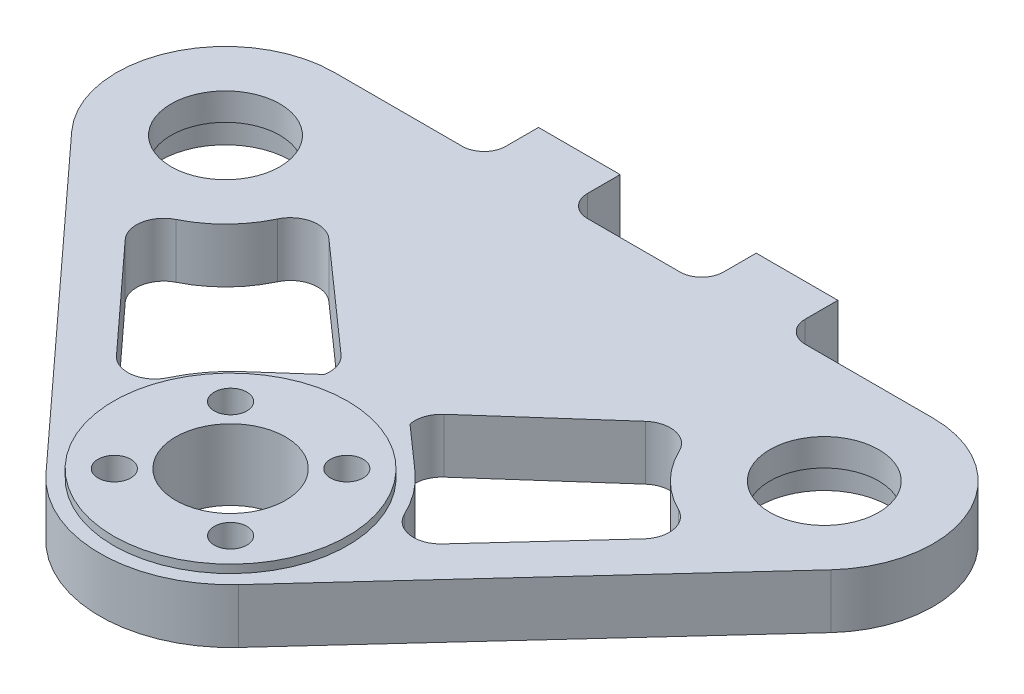
SolidWorks part; units mm, degrees
material "PLA Infill"
ref_plane "Front Plane" through (0, 0, 0) normal (0, 0, 1) x (1, 0, 0)
ref_plane "Top Plane" through (0, 0, 0) normal (0, 1, 0) x (1, 0, 0)
ref_plane "Right Plane" through (0, 0, 0) normal (1, 0, 0) x (0, 0, -1)
sketch "Sketch1" plane through (0, 0, 0) normal (0, 1, 0) x (1, 0, 0)
  line L0 (0, 0) -> (55, 54.0672) construction
  line L1 (55, 54.0672) -> (-55, 54.0672) construction
  line L2 (-55, 54.0672) -> (0, 0) construction
  line L3 (-69.7415, 40.551) -> (-17.6898, -16.2194)
  line L4 (-41.7379, 69.0378) -> (15.9145, 17.9646)
  line L5 (-47.6255, 28.2677) -> (-29.9271, 8.9649)
  line L6 (-29.0781, 47.135) -> (-9.4754, 29.7694)
  circle A0 centre (0, 0) radius 10.1
  circle A1 centre (-55, 54.0672) radius 10
  circle A2 centre (0, 0) radius 24 construction
  circle A3 centre (-55, 54.0672) radius 20 construction
  arc A4 (-69.7415, 40.551) -> (-41.7379, 69.0378) centre (-55, 54.0672) cw
  arc A5 (-17.6898, -16.2194) -> (15.9145, 17.9646) centre (0, 0) ccw
  arc A6 (-46.1521, 36.1308) -> (-36.9149, 45.5274) centre (-55, 54.0672) ccw
  arc A7 (-21.7173, 10.2157) -> (-10.5856, 21.5394) centre (0, 0) cw
  arc A8 (-29.9271, 8.9649) -> (-21.7173, 10.2157) centre (-26.2417, 12.3439) ccw
  arc A9 (-9.4754, 29.7694) -> (-10.5856, 21.5394) centre (-12.7909, 26.0268) cw
  arc A10 (-29.0781, 47.135) -> (-36.9149, 45.5274) centre (-32.3936, 43.3924) ccw
  arc A11 (-47.6255, 28.2677) -> (-46.1521, 36.1308) centre (-43.9401, 31.6467) cw
  point P22 (-23.8825, 2.3723)
  point P25 (-2.7804, 23.8384)
  point P28 (-35.0663, 52.4399)
  point P31 (-53.032, 34.1643)
  dimension "D3" = 20.2
  dimension "D4" = 20
  dimension "D5" = 48
  dimension "D6" = 40
  dimension "D9" = 5
  dimension "D1" = 77.125
  dimension "D2" = 110
  dimension "D7" = 8
  dimension "D8" = 8
extrude "Main Body" add sketch "Sketch1" along normal blind 10
sketch "Sketch2" plane through (0, 0, 0) normal (0, -1, 0) x (1, 0, 0)
  circle A0 centre (-55, -54.0672) radius 10 construction
  circle A1 centre (-55, -54.0672) radius 10 construction
  circle A2 centre (-55, -54.0672) radius 12
  dimension "D1" = 24
extrude "Bearing Recess" cut sketch "Sketch2" against normal blind 5
sketch "Sketch3" plane through (0, 0, 0) normal (0, -1, 0) x (1, 0, 0)
  circle A0 centre (0, 0) radius 21.5
  circle A1 centre (0, 0) radius 10.1
  circle A2 centre (0, 0) radius 10.1 construction
  dimension "D1" = 43
extrude "Standoff Section" add sketch "Sketch3" along normal blind 1.5 and the other way blind 11.5
ref_plane "Mirror Plane" through (0, 0, 0) normal (1, 0, 0) x (0, 0, -1)
sketch "Sketch6" plane through (0, 0, 0) normal (0, 1, 0) x (1, 0, 0)
  line L0 (-55, 74.0672) -> (0, 74.0672) construction
  line L1 (0, -7.15) -> (0, 7.15) construction
  line L2 (0, 74.0672) -> (0, 32.063)
  line L3 (-41.7379, 69.0378) -> (15.9145, 17.9646) construction
  line L4 (0, 32.063) -> (-41.7379, 69.0378)
  line L5 (-20, 84.0672) -> (-20, 74.0672) construction
  line L6 (-27.5, 74.0672) -> (-12.5, 74.0672) construction
  line L7 (-27.5, 78.0672) -> (-27.5, 84.0672)
  line L8 (-27.5, 84.0672) -> (-12.5, 84.0672)
  line L9 (-12.5, 78.0672) -> (-12.5, 84.0672)
  line L10 (-55, 74.0672) -> (-31.5, 74.0672)
  line L11 (-8.5, 74.0672) -> (0, 74.0672)
  arc A0 (-41.7379, 69.0378) -> (-69.7415, 40.551) centre (-55, 54.0672) ccw construction
  arc A1 (-41.7379, 69.0378) -> (-69.7415, 40.551) centre (-55, 54.0672) ccw construction
  arc A2 (-55, 74.0672) -> (-41.7379, 69.0378) centre (-55, 54.0672) cw
  arc A3 (-8.5, 74.0672) -> (-12.5, 78.0672) centre (-8.5, 78.0672) cw
  arc A4 (-31.5, 74.0672) -> (-27.5, 78.0672) centre (-31.5, 78.0672) ccw
  dimension "D4" = 4
  dimension "D1" = 10
  dimension "D2" = 20
  dimension "D3" = 15
extrude "Extra Geometry" add sketch "Sketch6" along normal blind 10
sketch "Sketch8" plane through (0, 0, -84.0672) normal (0, 0, -1) x (-1, 0, 0)
  line L0 (20, 10) -> (20, 0) construction
  line L1 (12.5, 10) -> (27.5, 10) construction
  line L2 (12.5, 0) -> (27.5, 0) construction
  circle A0 centre (20, 5) radius 2
  point P9 (20, 5)
  dimension "D1" = 4
extrude "Cut-Extrude1" cut sketch "Sketch8" against normal blind 6
mirror "Mirror2" about plane through (0, 0, 0) normal (1, 0, 0) of bodies 109 107
sketch "Sketch4" plane through (0, -1.5, 0) normal (0, -1, 0) x (1, 0, 0)
  line L0 (0, 0) -> (50000, 0) construction
  line L1 (55, -54.0672) -> (-55, -54.0672) construction
  line L2 (-10.6773, 10.6773) -> (0, 0) construction
  circle A0 centre (-10.6773, 10.6773) radius 3
  circle A2 centre (10.6773, 10.6773) radius 3
  circle A3 centre (10.6773, -10.6773) radius 3
  circle A4 centre (-10.6773, -10.6773) radius 3
  dimension "D1" = 6
  dimension "D2" = 15.1
  dimension "D3" = 45
  dimension "D4" = 4
extrude "M6 Bolt holes" cut sketch "Sketch4" against normal through all
